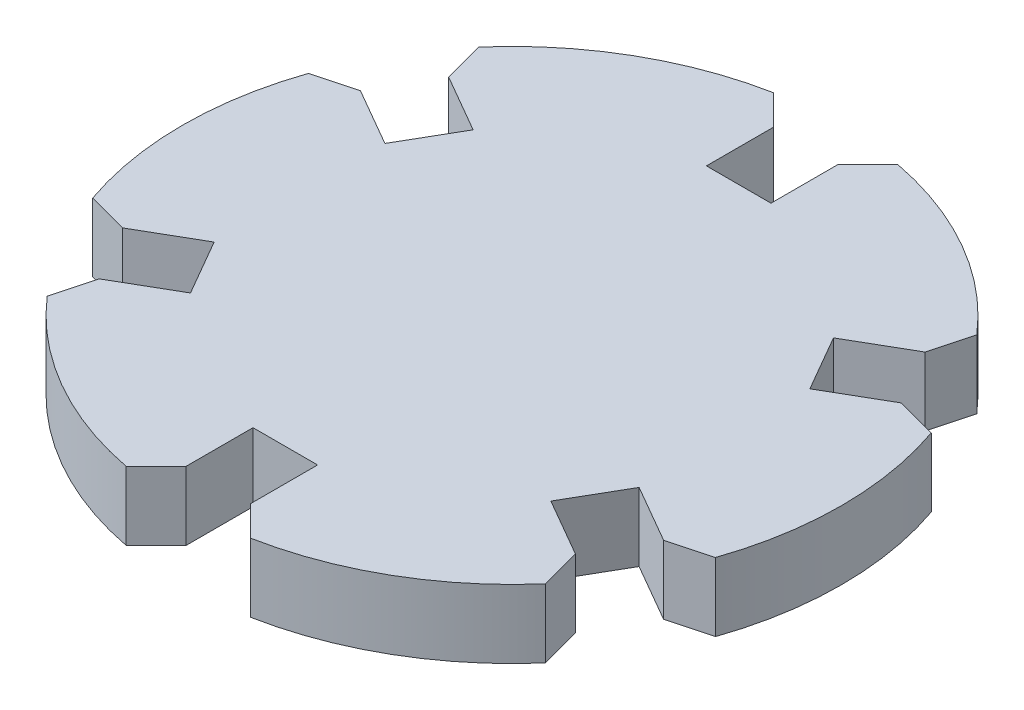
SolidWorks part; units mm, degrees
ref_plane "Front Plane" through (0, 0, 0) normal (0, 0, 1) x (1, 0, 0)
ref_plane "Top Plane" through (0, 0, 0) normal (0, 1, 0) x (1, 0, 0)
ref_plane "Right Plane" through (0, 0, 0) normal (1, 0, 0) x (0, 0, -1)
sketch "Sketch1" plane through (0, 0, 0) normal (0, 1, 0) x (1, 0, 0)
  circle A0 centre (0, 0) radius 25
  dimension "D1" = 50
extrude "Boss-Extrude1" add sketch "Sketch1" along normal blind 5.2
sketch "Sketch2" plane through (0, 5.2, 0) normal (0, 1, 0) x (1, 0, 0)
  line L0 (22.8756, 10.3782) -> (16.1206, 6.4782)
  line L1 (-2.45, 25) -> (2.45, 25)
  line L2 (-2.45, 25) -> (-2.45, 17.2)
  line L3 (-2.45, 17.2) -> (2.45, 17.2)
  line L4 (2.45, 25) -> (2.45, 17.2)
  line L5 (20.4256, 14.6218) -> (22.8756, 10.3782)
  line L6 (20.4256, 14.6218) -> (13.6706, 10.7218)
  line L7 (13.6706, 10.7218) -> (16.1206, 6.4782)
  line L8 (20.4256, -14.6218) -> (13.6706, -10.7218)
  line L9 (22.8756, -10.3782) -> (20.4256, -14.6218)
  line L10 (22.8756, -10.3782) -> (16.1206, -6.4782)
  line L11 (16.1206, -6.4782) -> (13.6706, -10.7218)
  line L12 (-2.45, -25) -> (-2.45, -17.2)
  line L13 (2.45, -25) -> (-2.45, -25)
  line L14 (2.45, -25) -> (2.45, -17.2)
  line L15 (2.45, -17.2) -> (-2.45, -17.2)
  line L16 (-22.8756, -10.3782) -> (-16.1206, -6.4782)
  line L17 (-20.4256, -14.6218) -> (-22.8756, -10.3782)
  line L18 (-20.4256, -14.6218) -> (-13.6706, -10.7218)
  line L19 (-13.6706, -10.7218) -> (-16.1206, -6.4782)
  line L20 (-20.4256, 14.6218) -> (-13.6706, 10.7218)
  line L21 (-22.8756, 10.3782) -> (-20.4256, 14.6218)
  line L22 (-22.8756, 10.3782) -> (-16.1206, 6.4782)
  line L23 (-16.1206, 6.4782) -> (-13.6706, 10.7218)
  circle A0 centre (0, 0) radius 25 construction
  point P4 (0, 17.2)
  dimension "D1" = 4.9
  dimension "D2" = 7.8
  dimension "D3" = 6
extrude "Cut-Extrude1" cut sketch "Sketch2" against normal blind 5.2
chamfer "Chamfer1" distance 2.6 angle 45 12 edges at (2.45, 2.6, -24.8797) (-2.45, 2.6, -24.8797) (22.7714, 2.6, -10.3181) (20.3214, 2.6, -14.5616) (22.7714, 2.6, 10.3181) (20.3214, 2.6, 14.5616) (2.45, 2.6, 24.8797) (-2.45, 2.6, 24.8797) (-20.3214, 2.6, 14.5616) (-22.7714, 2.6, 10.3181) (-22.7714, 2.6, -10.3181) (-20.3214, 2.6, -14.5616) first distance on face at (2.45, 2.6, -21.0398) first distance on face at (-2.45, 2.6, -21.0398) first distance on face at (19.446, 2.6, -8.3982) first distance on face at (16.996, 2.6, -12.6417) first distance on face at (19.446, 2.6, 8.3982) first distance on face at (16.996, 2.6, 12.6417) first distance on face at (2.45, 2.6, 21.0398) first distance on face at (-2.45, 2.6, 21.0398) first distance on face at (-16.996, 2.6, 12.6417) first distance on face at (-19.446, 2.6, 8.3982) first distance on face at (-19.446, 2.6, -8.3982) first distance on face at (-16.996, 2.6, -12.6417)
equation "\"thick\"= 5.2'board thickness"
equation "\"fit\"= 0.3mm'fit adjustment"
equation "\"depth\"= \"thick\" * 1.5'cut depth"
equation "\"chamfer\"= \"thick\" / 2'fillet radius"
equation "\"width\"= \"thick\" - \"fit\"'cut width"
equation "\"gap\"= \"depth\" * 2'cut gap"
equation "\"curv\"= \"gap\" * 2'curvature radius"
equation "\"D1@Sketch2\"=\"width\""
equation "\"D2@Sketch2\"=\"depth\""
equation "\"D1@Chamfer1\"=\"chamfer\""
